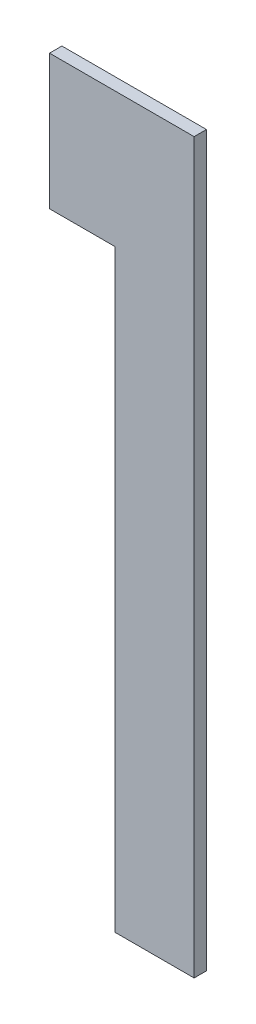
SolidWorks part; units mm, degrees
ref_plane "Front Plane" through (0, 0, 0) normal (0, 0, 1) x (1, 0, 0)
ref_plane "Top Plane" through (0, 0, 0) normal (0, 1, 0) x (1, 0, 0)
ref_plane "Right Plane" through (0, 0, 0) normal (1, 0, 0) x (0, 0, -1)
sketch "Sketch1" plane through (0, 0, 0) normal (0, 0, 1) x (1, 0, 0)
  line L0 (59.51, 68.95) -> (54.51, 68.95) construction
  line L1 (0, 0) -> (7.5, 0)
  line L3 (-6.1826, 68.95) -> (7.5, 68.95)
  line L4 (7.5, 0) -> (7.5, 68.95)
  line L5 (0, 0) -> (0, 56.1945)
  line L6 (0, 56.1945) -> (-6.1826, 56.1945)
  line L7 (-6.1826, 56.1945) -> (-6.1826, 68.95)
base flange "Base-Flange1" sketch "Sketch1" thickness 1.17 reverse thickness direction no parameters "D1"=1.65
sketch "Bend-Lines1" [suppressed] plane through (0, 0, 0) normal (0, 1, 0) x (1, 0, 0)
sketch "Bounding-Box1" [suppressed] plane through (0, 0, 0) normal (0, 1, 0) x (1, 0, 0)
sheet metal parameters "Sheet-Metal1" thickness 1.17 parameters "D1"=1.65
flat pattern "Flat-Pattern1" [suppressed]
sketch "Bend-Lines2" plane through (0, 0, 0) normal (0, 1, 0) x (1, 0, 0)
sketch3d "Bounding-Box2" [suppressed]
  line L0 (7.5, 68.95, 0) -> (7.5, 0, 0) construction
  line L1 (-6.1826, 68.95, 0) -> (-6.1826, 0, 0) construction
  line L2 (7.5, 68.95, 0) -> (-6.1826, 68.95, 0) construction
  line L3 (7.5, 0, 0) -> (-6.1826, 0, 0) construction
